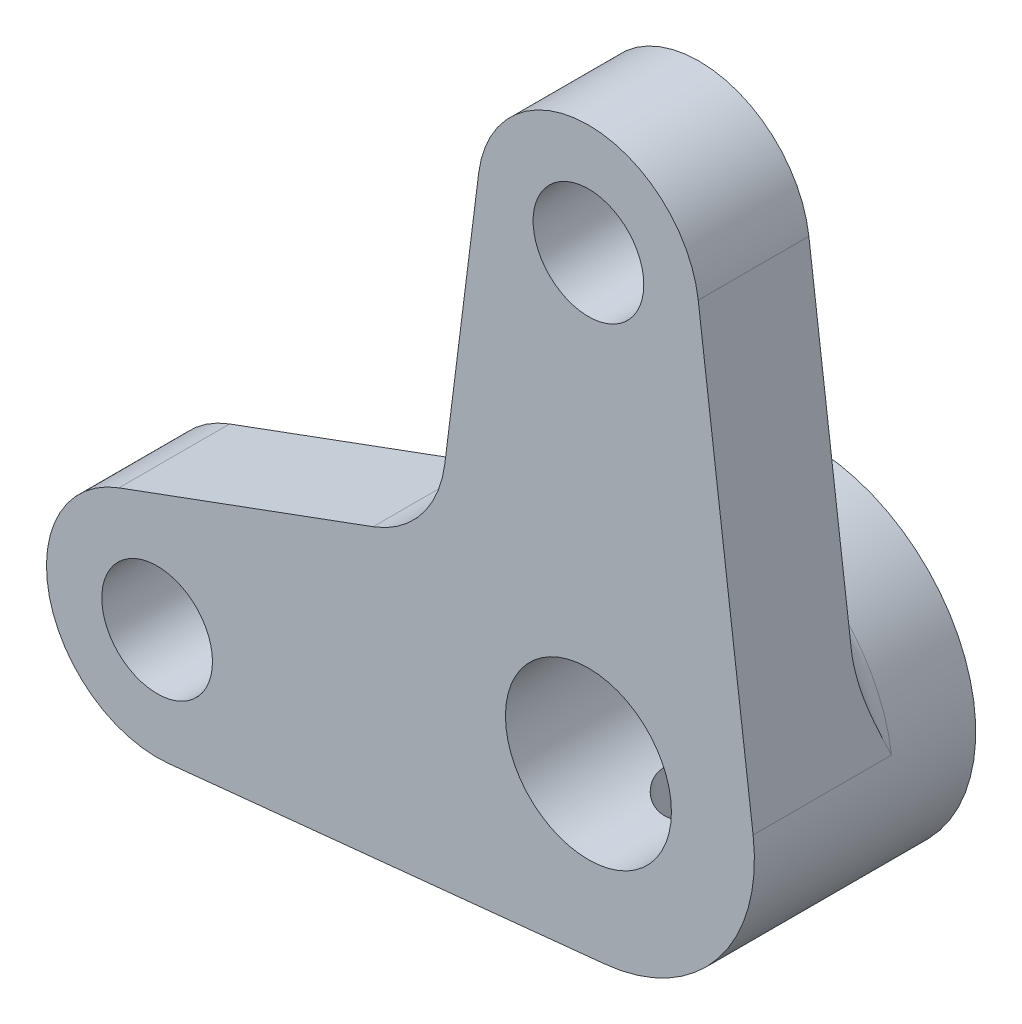
SolidWorks part; units mm, degrees
ref_plane "Front Plane" through (0, 0, 0) normal (0, 0, 1) x (1, 0, 0)
ref_plane "Top Plane" through (0, 0, 0) normal (0, 1, 0) x (1, 0, 0)
ref_plane "Right Plane" through (0, 0, 0) normal (1, 0, 0) x (0, 0, -1)
sketch "Sketch1" plane through (0, 0, 0) normal (0, 0, 1) x (1, 0, 0)
  line L0 (0, 0) -> (0, 3) construction
  line L1 (0, 0) -> (-5.8462, -1.3497) construction
  line L2 (-16.9699, 0.1552) -> (-7.781, 3.5325)
  line L3 (-15.1844, -7.5786) -> (0.6083, -5.9691)
  line L4 (3.9686, 16.5) -> (5.9529, 0.75)
  line L5 (-3.9686, 16.5) -> (-5.1924, 6.787)
  line L6 (0, 6) -> (0, 16) construction
  line L7 (-11.6924, -2.6994) -> (-15.5899, -3.5992) construction
  arc A0 (-16.9699, 0.1552) -> (-15.1844, -7.5786) centre (-15.5899, -3.5992) ccw
  circle A1 centre (-15.5899, -3.5992) radius 2
  arc A2 (0.6083, -5.9691) -> (5.9529, 0.75) centre (0, 0) ccw
  circle A3 centre (0, 0) radius 3
  circle A4 centre (0, 16) radius 2
  arc A5 (3.9686, 16.5) -> (-3.9686, 16.5) centre (0, 16) ccw
  arc A6 (-5.1924, 6.787) -> (-7.781, 3.5325) centre (-9.161, 7.287) cw
  dimension "D4" = 8
  dimension "D5" = 4
  dimension "D6" = 6
  dimension "D7" = 12
  dimension "D8" = 8
  dimension "D9" = 4
  dimension "D10" = 4
  dimension "D1" = 16
  dimension "D2" = 16
  dimension "D3" = 103
extrude "Boss-Extrude1" add sketch "Sketch1" along normal blind 4
sketch "Sketch2" plane through (0, 0, 0) normal (0, 0, -1) x (-1, 0, 0)
  circle A0 centre (0, 0) radius 3
  circle A1 centre (0, 0) radius 6
  dimension "D1" = 12
  dimension "D2" = 6
extrude "Boss-Extrude2" add sketch "Sketch2" along normal blind 4
sketch "Sketch4" plane through (0, 0, -4) normal (0, 0, -1) x (-1, 0, 0)
  line L0 (-6.3995, -7) -> (5.1674, -7)
  dimension "D1" = 7
extrude "Extrude-Thin1" add sketch "Sketch4" against normal blind 8 separate body thin thin type one direction wall 1
hole_wizard "M3x0.5 Tapped Hole1" positions "Sketch5" profile "Sketch6" tap size "M3x0.5" standard "ANSI Metric"
sketch "Sketch5" plane through (0, -8, 0) normal (0, -1, 0) x (-1, 0, 0)
  point P0 (0, 0)
sketch "Sketch6" plane through (0, -8, 0) normal (1, 0, 0) x (0, 0, -1)
  line L0 (0, 0) -> (0, 8.2511)
  line L1 (0, 8.2511) -> (1.25, 7.5)
  line L2 (1.25, 7.5) -> (1.25, 0.275)
  line L3 (1.25, 0.275) -> (1.525, 0)
  line L5 (1.525, 0) -> (0, 0)
  line L6 (-1.25, 0.275) -> (-1.525, 0) construction
  line L10 (0, 8.2511) -> (-1.25, 7.5) construction
  line L11 (0, -6.35) -> (0, 107.95) construction
  dimension "Tap Drill Dia." = 2.5
  dimension "Tap Drill Depth" = 7.5
  dimension "Near C'Sink Dia." = 3.05
  dimension "Near C'Sink Angle" = 90
  dimension "Drill Angle" = 118
cosmetic thread "Hole Thread1" parameters "D1"=5.2728, "D2"=3
sketch "Sketch7" plane through (0, 0, -4) normal (0, 0, -1) x (-1, 0, 0)
  line L1 (5.1674, -7) -> (-6.3995, -7)
  line L2 (5.1674, -7) -> (5.1674, -8)
  line L3 (5.1674, -8) -> (-6.3995, -8)
  line L4 (-6.3995, -7) -> (-6.3995, -8)
extrude "Cut-Extrude1" cut sketch "Sketch7" against normal blind 8
fillet "Fillet5" radius 1 1 edges at (-4.0596, 4.4181, 0)
